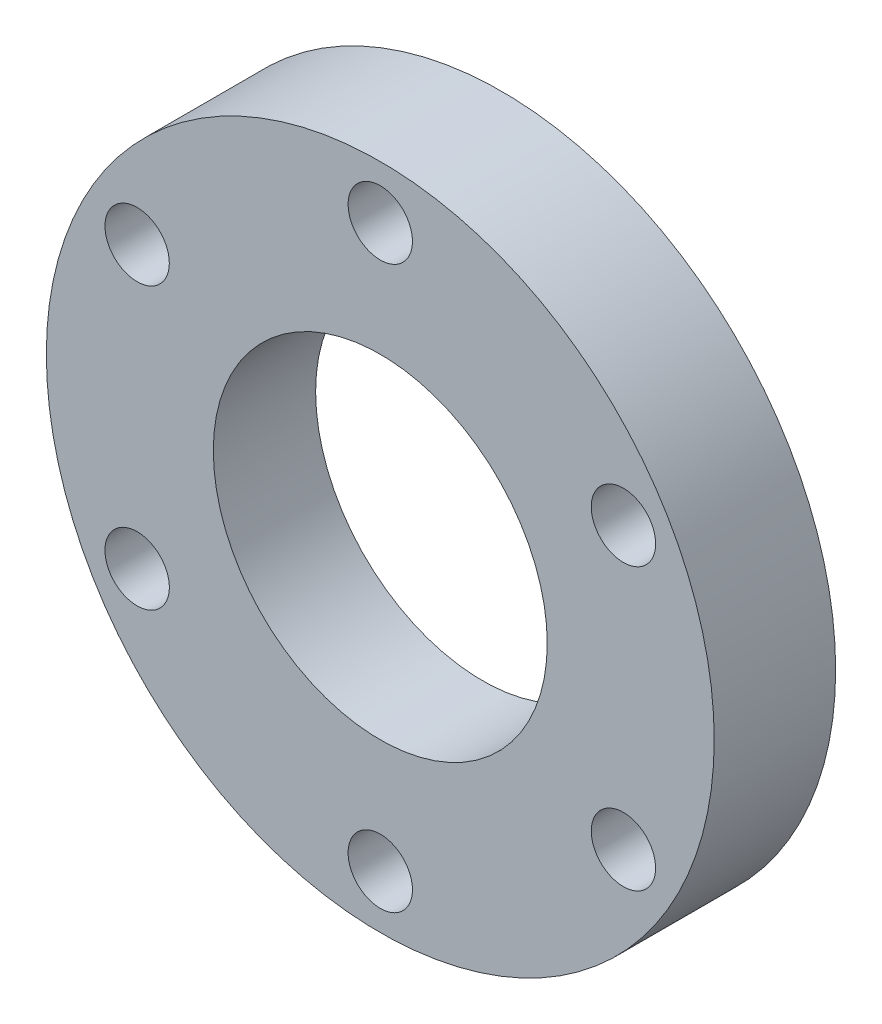
SolidWorks part; units mm, degrees
ref_plane "Front" through (0, 0, 0) normal (0, 0, 1) x (1, 0, 0)
ref_plane "Top" through (0, 0, 0) normal (0, 1, 0) x (1, 0, 0)
ref_plane "Right" through (0, 0, 0) normal (1, 0, 0) x (0, 0, -1)
sketch "Sketch1" plane through (0, 0, 0) normal (0, 0, 1) x (1, 0, 0)
  circle A0 centre (0, 0) radius 34.925
  circle A1 centre (0, 0) radius 8
extrude "Base-Extrude" add sketch "Sketch1" along normal blind 12.7
sketch "Sketch6" plane through (0, 0, 0) normal (0, 0, -1) x (-1, 0, 0)
  circle A0 centre (0, 29.3624) radius 3.3655
extrude "Cut-Extrude1" cut sketch "Sketch6" against normal through all
sketch "Sketch9" plane through (0, 0, 0) normal (1, 0, 0) x (0, 0, -1)
  line L0 (-12.7, 0) -> (0, 0)
  line L1 (-12.7, 0) -> (0, 0) construction
ref_axis "Axis2" through (0, 0, 0) along (0, 0, 1)
pattern_circular "CirPattern2" count 6 over 360 about axis through (0, 0, 0) along (0, 0, 1) of "Cut-Extrude1"
sketch "Sketch11" plane through (0, 0, 0) normal (0, 0, -1) x (-1, 0, 0)
  circle A0 centre (0, 0) radius 23.0712
extrude "Cut-Extrude3" cut sketch "Sketch11" against normal blind 2
sketch "Sketch12" plane through (0, 0, 12.7) normal (0, 0, 1) x (1, 0, 0)
  circle A0 centre (0, 0) radius 11.5
extrude "Cut-Extrude4" cut sketch "Sketch12" against normal blind 2
sketch "Sketch14" plane through (0, 0, 12.7) normal (0, 0, 1) x (1, 0, 0)
  circle A0 centre (0, 0) radius 17.4625
extrude "Cut-Extrude5" cut sketch "Sketch14" against normal through all
